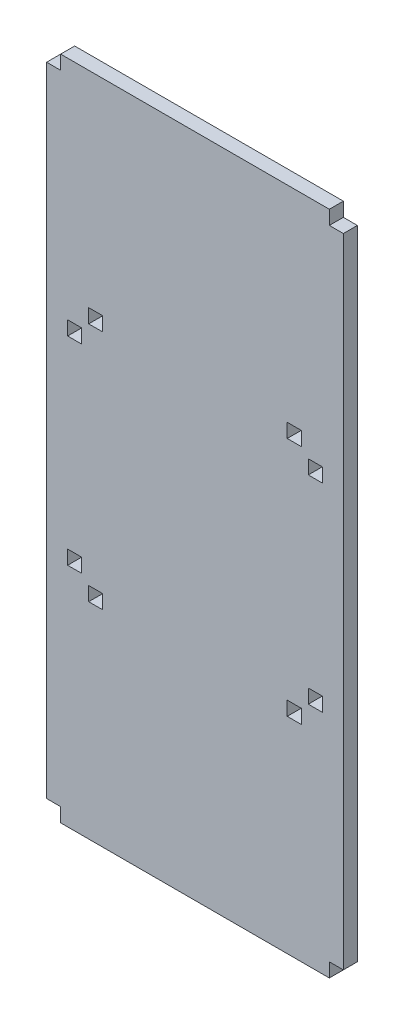
SolidWorks part; units mm, degrees
ref_plane "Front Plane" through (0, 0, 0) normal (0, 0, 1) x (1, 0, 0)
ref_plane "Top Plane" through (0, 0, 0) normal (0, 1, 0) x (1, 0, 0)
ref_plane "Right Plane" through (0, 0, 0) normal (1, 0, 0) x (0, 0, -1)
sketch "Sketch1" plane through (0, 0, 0) normal (0, 0, 1) x (1, 0, 0)
  line L0 (0, -0.9075) -> (0, 0.9075) construction
  line L1 (-15.8, 39.15) -> (15.8, 39.15)
  line L2 (-15.8, 39.15) -> (-15.8, -39.15)
  line L3 (-15.8, -39.15) -> (15.8, -39.15)
  line L4 (15.8, 39.15) -> (15.8, -39.15)
  line L5 (0.9075, 0) -> (-0.9075, 0) construction
  point P5 (0, 39.15)
  point P8 (15.8, 0)
  dimension "D1" = 78.3
  dimension "D2" = 31.6
extrude "Boss-Extrude1" add sketch "Sketch1" along normal blind 1.65
sketch "Sketch3" plane through (-15.8, 0, 0) normal (-1, 0, 0) x (0, 0, 1)
  line L0 (1.65, 39.15) -> (1.65, -39.15) construction
  line L1 (1.65, 37.5) -> (0, 37.5)
  line L2 (1.65, 37.5) -> (1.65, -37.5)
  line L3 (1.65, -37.5) -> (0, -37.5)
  line L4 (0, 37.5) -> (0, -37.5)
  line L5 (0, 39.15) -> (0, -39.15) construction
  line L6 (1.65, -39.15) -> (0, -39.15) construction
  line L7 (1.65, 39.15) -> (0, 39.15) construction
  dimension "D1" = 1.65
  dimension "D2" = 1.65
extrude "Boss-Extrude2" add sketch "Sketch3" along normal blind 1.65
mirror "Mirror1" about plane through (0, 0, 0) normal (1, 0, 0) of "Boss-Extrude2"
sketch "Sketch2" plane through (0, 0, 1.65) normal (0, 0, 1) x (1, 0, 0)
  line L0 (0.9075, 0) -> (-0.9075, 0) construction
  line L1 (13.325, 12.5) -> (14.975, 12.5)
  line L2 (13.325, 12.5) -> (13.325, -12.5)
  line L3 (13.325, -12.5) -> (14.975, -12.5)
  line L4 (14.975, 12.5) -> (14.975, -12.5)
  line L6 (0, -0.9075) -> (0, 0.9075) construction
  line L7 (12.5, -13.325) -> (12.5, -14.975)
  line L8 (12.5, -13.325) -> (-12.5, -13.325)
  line L9 (-12.5, -13.325) -> (-12.5, -14.975)
  line L10 (12.5, -14.975) -> (-12.5, -14.975)
  line L11 (-13.325, -12.5) -> (-14.975, -12.5)
  line L12 (-13.325, -12.5) -> (-13.325, 12.5)
  line L13 (-13.325, 12.5) -> (-14.975, 12.5)
  line L14 (-14.975, -12.5) -> (-14.975, 12.5)
  line L15 (-12.5, 13.325) -> (-12.5, 14.975)
  line L16 (-12.5, 13.325) -> (12.5, 13.325)
  line L17 (12.5, 13.325) -> (12.5, 14.975)
  line L18 (-12.5, 14.975) -> (12.5, 14.975)
  line L19 (13.325, 10.85) -> (14.975, 10.85)
  line L20 (13.325, -10.85) -> (14.975, -10.85)
  line L21 (-10.85, -13.325) -> (-10.85, -14.975)
  line L22 (10.85, -13.325) -> (10.85, -14.975)
  line L23 (-13.325, 10.85) -> (-14.975, 10.85)
  line L24 (-13.325, -10.85) -> (-14.975, -10.85)
  line L25 (10.85, 13.325) -> (10.85, 14.975)
  line L26 (-10.85, 13.325) -> (-10.85, 14.975)
  point P4 (14.975, 0)
  point P8 (14.15, -12.5)
  dimension "D1" = 1.65
  dimension "D2" = 25
  dimension "D3" = 14.15
  dimension "D5" = 1.65
  dimension "D6" = 1.65
  dimension "D4" = 4
  dimension "D7" = 4
extrude "Cut-Extrude1" cut sketch "Sketch2" against normal blind 1.65 contours L8 L22 L10 L7 | L21 L8 L9 L10 | L12 L24 L14 L11 | L23 L12 L13 L14 | L16 L26 L18 L15 | L25 L16 L17 L18 | L2 L19 L4 L1 | L20 L2 L3 L4 region at (14.15, 11.675, 1.65) region at (14.15, -11.675, 1.65) region at (11.675, -14.15, 1.65) region at (-11.675, -14.15, 1.65) region at (-14.15, -11.675, 1.65) region at (-14.15, 11.675, 1.65) region at (-11.675, 14.15, 1.65) region at (11.675, 14.15, 1.65)
sketch "Sketch4" [suppressed] plane through (0, -39.15, 0) normal (0, -1, 0) x (1, 0, 0)
  line L0 (-15.8, 1.65) -> (15.8, 1.65) construction
  line L1 (-14.15, 1.65) -> (14.15, 1.65)
  line L2 (-14.15, 1.65) -> (-14.15, 0)
  line L3 (-14.15, 0) -> (14.15, 0)
  line L4 (14.15, 1.65) -> (14.15, 0)
  line L5 (-15.8, 0) -> (15.8, 0) construction
  line L6 (15.8, 0) -> (15.8, 1.65) construction
  line L7 (-15.8, 1.65) -> (-15.8, 0) construction
  dimension "D1" = 1.65
  dimension "D2" = 1.65
extrude "Cut-Extrude2" [suppressed] cut sketch "Sketch4" against normal blind 1.65
mirror "Mirror2" [suppressed] about plane through (0, 0, 0) normal (0, 1, 0)
equation "\"D1@Sketch1\"=3/8 * \"lenght\" + \"PCB Thickness\" * 2"
equation "\"Dinoskin scale\"= 2"
equation "\"pattern X\"= 3"
equation "\"Pattern Y\"= 11"
equation "\"Base Innerline\"= 0.34"
equation "\"lenght\"= 200"
equation "\"PCB Thickness\"= 1.65"
equation "\"Base Width\"= 4.3"
equation "\"Base Outerline\"= 0.45"
equation "\"Base Inner to Outer\"= 1"
equation "\"Dinoskin Outerline\"= \"Base Outerline\" * \"Dinoskin scale\""
equation "\"Dinoskin Innerline\"= \"Base Innerline\" * \"Dinoskin scale\""
equation "\"Dinoskin Width\"= \"Base Width\" * \"Dinoskin scale\""
equation "\"Dinoskin Inner to Outer\"= \"Base Inner to Outer\" * \"Dinoskin scale\""
equation "\"Diagonal dist\"= \"Dinoskin Width\" + ( ( \"Dinoskin Innerline\" + \"Dinoskin Outerline\" ) / 2 + \"Dinoskin Inner to Outer\" ) / cos ( 30 )"
equation "\"Dinoskin pattern Y\"= \"Diagonal dist\" * sin ( 30 )"
equation "\"Offset Y\"= 2 * \"Dinoskin pattern Y\""
equation "\"Diagonal dist 2\"= \"Dinoskin Width\" + ( ( \"Dinoskin Innerline\" + \"Dinoskin Outerline\" ) / 2 + 1 ) / cos ( 30 )"
equation "\"Dinoskin pattern X\"= \"Diagonal dist\" * cos ( 30 )"
equation "\"offset x\"= \"Dinoskin pattern X\" * 2"
equation "\"Pattern spacing X\"= \"offset x\" * ( \"pattern X\" - 0.5 ) / 2"
equation "\"Pattern spacing Y\"= \"Offset Y\" *  ( \"Pattern Y\" - 0.5 )  / 2 + 13"
equation "\"offset corner beams\" = 1"
equation "\"D2@Sketch1\"=\"lenght\" / 8 + \"PCB Thickness\" * 4"
equation "\"D1@Boss-Extrude1\"= \"PCB Thickness\""
equation "\"D1@Sketch2\"= \"PCB Thickness\""
equation "\"D2@Sketch2\"= \"lenght\" / 8"
equation "\"D1@Sketch3\"= \"PCB Thickness\""
equation "\"D2@Sketch3\"=\"PCB Thickness\""
equation "\"D1@Boss-Extrude2\"=\"PCB Thickness\""
equation "\"D3@Sketch2\"=\"lenght\"/16 + \"PCB Thickness\""
equation "\"D5@Sketch2\"= \"PCB Thickness\""
equation "\"D6@Sketch2\"=\"PCB Thickness\""
equation "\"D1@Sketch4\"= \"PCB Thickness\""
equation "\"D2@Sketch4\"= \"PCB Thickness\""
equation "\"D1@Cut-Extrude2\"= \"PCB Thickness\""
